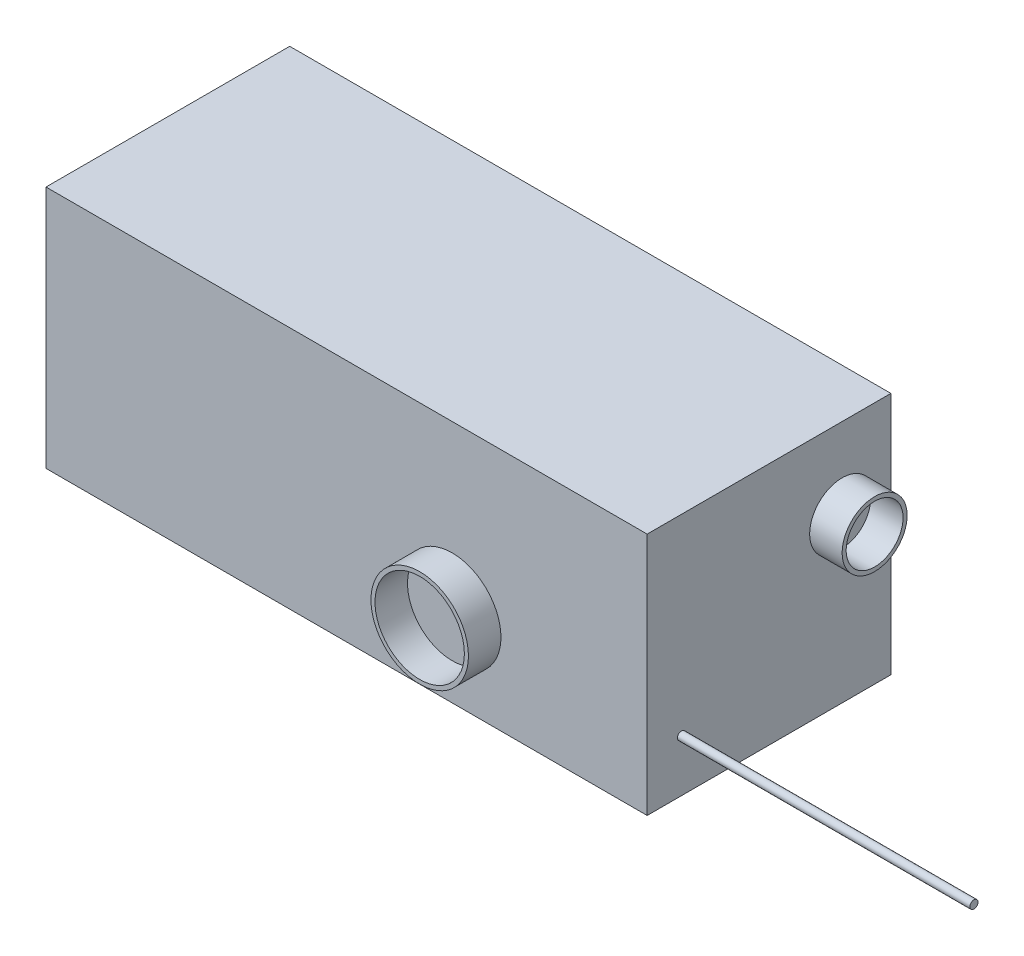
SolidWorks part; units mm, degrees
ref_plane "Front" through (0, 0, 0) normal (0, 0, 1) x (1, 0, 0)
ref_plane "Top" through (0, 0, 0) normal (0, 1, 0) x (1, 0, 0)
ref_plane "Right" through (0, 0, 0) normal (1, 0, 0) x (0, 0, -1)
sketch "Sketch1" plane through (0, 0, 0) normal (0, 1, 0) x (1, 0, 0)
  line L1 (-469.9, 190.5) -> (469.9, 190.5)
  line L2 (-469.9, 190.5) -> (-469.9, -190.5)
  line L3 (-469.9, -190.5) -> (469.9, -190.5)
  line L4 (469.9, 190.5) -> (469.9, -190.5)
  line L5 (-469.9, 190.5) -> (469.9, -190.5) construction
  line L6 (-469.9, -190.5) -> (469.9, 190.5) construction
  point P0 (0, 0)
  dimension "D1" = 381
  dimension "D2" = 939.8
extrude "Boss-Extrude1" add sketch "Sketch1" along normal blind 381
sketch "Sketch2" plane through (0, 0, 190.5) normal (0, 0, 1) x (1, 0, 0)
  line L0 (469.9, 381) -> (469.9, 0) construction
  line L1 (-469.9, 381) -> (469.9, 381) construction
  circle A0 centre (165.1, 127) radius 76.2
  circle A1 centre (165.1, 127) radius 69.85
  dimension "D1" = 152.4
  dimension "D3" = 254
  dimension "D4" = 139.7
  dimension "D2" = 304.8
extrude "Boss-Extrude2" add sketch "Sketch2" along normal blind 50.8
sketch "Sketch3" plane through (469.9, 0, 0) normal (1, 0, 0) x (0, 0, -1)
  line L0 (-190.5, 381) -> (190.5, 381) construction
  line L1 (190.5, 381) -> (190.5, 0) construction
  circle A0 centre (114.3, 254) radius 50.8
  circle A1 centre (114.3, 254) radius 44.45
  point P3 (115.0945, 259.2021)
  dimension "D1" = 101.6
  dimension "D2" = 88.9
  dimension "D3" = 127
  dimension "D4" = 76.2
extrude "Boss-Extrude3" add sketch "Sketch3" along normal blind 50.8
sketch "Sketch4" plane through (469.9, 0, 0) normal (1, 0, 0) x (0, 0, -1)
  circle A0 centre (-136.8501, 81.3511) radius 6.35
  dimension "D1" = 12.7
extrude "Boss-Extrude4" add sketch "Sketch4" along normal blind 457.2
sketch "Sketch5" plane through (0, 0, -190.5) normal (0, 0, -1) x (-1, 0, 0)
  line L0 (-469.9, 381) -> (469.9, 381) construction
  line L1 (469.9, 381) -> (469.9, 0) construction
  circle A0 centre (185.6926, 273.8882) radius 50.8
  circle A1 centre (185.6926, 273.8882) radius 44.45
  dimension "D1" = 101.6
  dimension "D2" = 88.9
  dimension "D4" = 284.2074
  dimension "D3" = 107.1118
extrude "Boss-Extrude5" add sketch "Sketch5" along normal blind 50.8
sketch "Sketch6" plane through (-469.9, 0, 0) normal (-1, 0, 0) x (0, 0, 1)
  line L0 (-190.5, 381) -> (190.5, 0) construction
  circle A0 centre (0, 190.5) radius 76.2
  circle A1 centre (0, 190.5) radius 69.85
  dimension "D1" = 152.4
  dimension "D2" = 139.7
extrude "Boss-Extrude6" add sketch "Sketch6" along normal blind 50.8
